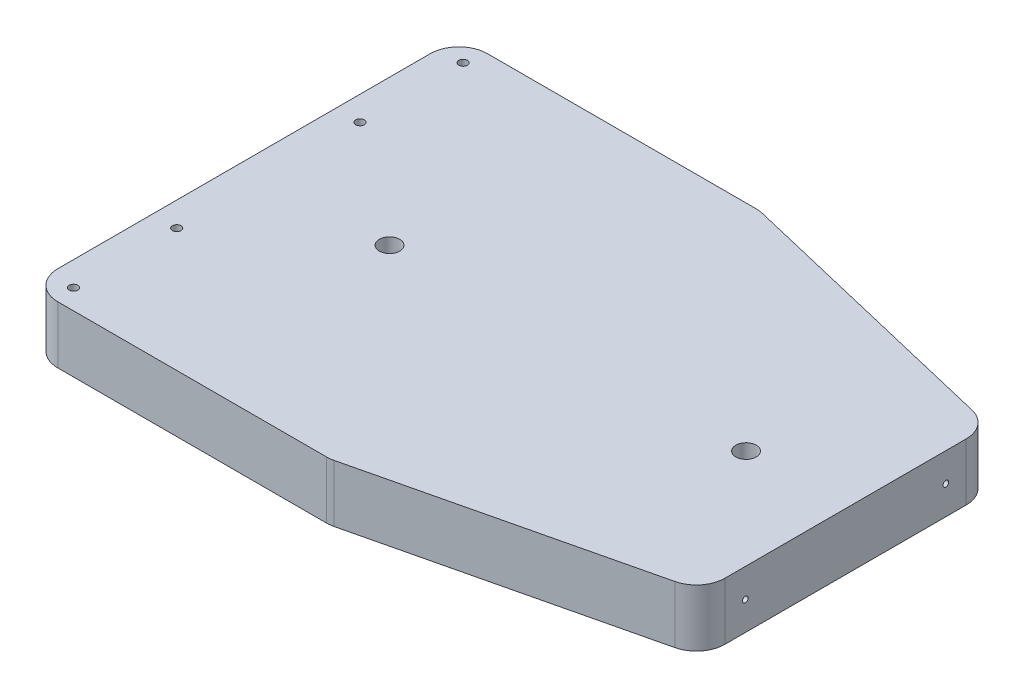
SolidWorks part; units mm, degrees
material "Carvalho"
ref_plane "Plano frontal" through (0, 0, 0) normal (0, 0, 1) x (1, 0, 0)
ref_plane "Plano superior" through (0, 0, 0) normal (0, 1, 0) x (1, 0, 0)
ref_plane "Plano direito" through (0, 0, 0) normal (1, 0, 0) x (0, 0, -1)
sketch "Esboço1" plane through (0, 0, 0) normal (0, 1, 0) x (1, 0, 0)
  line L0 (210, 50) -> (105, 75)
  line L1 (0, -75) -> (105, -75)
  line L2 (0, -75) -> (0, 75)
  line L3 (0, 75) -> (105, 75)
  line L4 (210, -50) -> (210, 50)
  line L5 (195, -38.5714) -> (210, -38.5714) construction
  line L6 (195, -38.5714) -> (195, -53.5714) construction
  line L7 (105, -75) -> (210, -50)
  line L8 (-14.8259, 0) -> (14.392, 0) construction
  line L9 (0, 21.2472) -> (0, -16.7598) construction
  circle A0 centre (50.8, 0) radius 3.5719
  circle A1 centre (175.26, 0) radius 3.57
  circle A2 centre (8.5, -68) radius 1.5
  circle A3 centre (8.5, -32) radius 1.5
  circle A4 centre (8.5, 32) radius 1.5
  circle A5 centre (8.5, 68) radius 1.5
  circle A6 centre (195, -38.5714) radius 0.5
  circle A7 centre (195, 38.5714) radius 0.5
  point P0 (0, 0)
  dimension "D3" = 7.1437
  dimension "D5" = 7.14
  dimension "D9" = 1
  dimension "D1" = 25
  dimension "D2" = 150
  dimension "D4" = 50.8
  dimension "D6" = 210
  dimension "D7" = 175.26
  dimension "D8" = 105
  dimension "D10" = 15
  dimension "D11" = 15
extrude "Ressalto-extrusão1" add sketch "Esboço1" along normal blind 15 and the other way blind 5 contours L1 L7 L4 L0 L3 L2 A0 A1 A2 A3 A4 A5 A6 A7 | A6 | A7 region at (98.6797, 0, 0)
sketch "Esboço2" plane through (210, 0, 0) normal (1, 0, 0) x (0, 0, -1)
  line L0 (0, -5) -> (0, 15) construction
  line L1 (-50, -5) -> (50, -5) construction
  line L2 (-50, 15) -> (50, 15) construction
  circle A0 centre (-35, 5) radius 1
  circle A1 centre (35, 5) radius 1
  point P8 (0, 5)
  dimension "D2" = 2
  dimension "D1" = 35
extrude "Corte-extrusão1" cut sketch "Esboço2" against normal blind 10
fillet "Filete1" radius 10 6 edges at (0, 5, 75) (105, 5, 75) (210, 5, 50) (210, 5, -50) (0, 5, -75) (105, 5, -75)
sketch "Esboço6" plane through (0, 15, 0) normal (0, 1, 0) x (1, 0, 0)
  line L0 (195, 38.1521) -> (195, -38.1521)
  line L2 (65, -60) -> (65, 60)
  line L4 (210, -42.1014) -> (210, 42.1014) construction
  line L5 (202.3162, 51.8295) -> (106.1421, 74.7281) construction
  line L8 (-4.1061, 0) -> (243.1802, 0) construction
  line L9 (65, 60) -> (103.2389, 60)
  line L10 (103.2389, 60) -> (195, 38.1521)
  line L11 (65, -60) -> (103.2389, -60)
  line L12 (103.2389, -60) -> (195, -38.1521)
  line L15 (175, -22.3549) -> (195, -17.593)
  line L16 (175, -42.914) -> (175, -22.3549)
  line L17 (103.8259, 75) -> (10, 75) construction
  line L18 (0, 65) -> (0, -65) construction
  line L19 (175, 22.3549) -> (195, 17.593)
  arc A0 (175, -22.3549) -> (175, 22.3549) centre (175.26, 0) cw
  circle A2 centre (175.26, 0) radius 3.57 construction
  point P20 (0, 0)
  point P24 (175, 22.3549)
  point P25 (175, 22.3549)
  point P26 (0, 0)
  point P27 (0, 0)
  point P28 (175, 0)
  point P31 (0, 0)
  circle M45 centre (175.26, 0) radius 3.57
  dimension "D1" = 15
  dimension "D2" = 15
  dimension "D3" = 15
  dimension "D4" = 65
  dimension "D5" = 20
  dimension "D6" = 20
extrude "Corte-extrusão2" cut sketch "Esboço6" along normal blind 10 from surface contours L8 L2 L11 L12 L16 L15 L0 M45 | L2 L8 L0 L10 L9 M45 region at (118.3408, 15, -28.8599) region at (113.4465, 15, 28.7576) starting at face at (105.3184, -5, 0)
fillet "Filete2" radius 10 8 edges at (65, 0, 60) (65, 0, -60) (103.2389, 0, -60) (195, 0, -17.593) (175, 0, -22.3549) (175, 0, 22.3549) (175, 0, 42.914) (195, 0, -38.1521)
